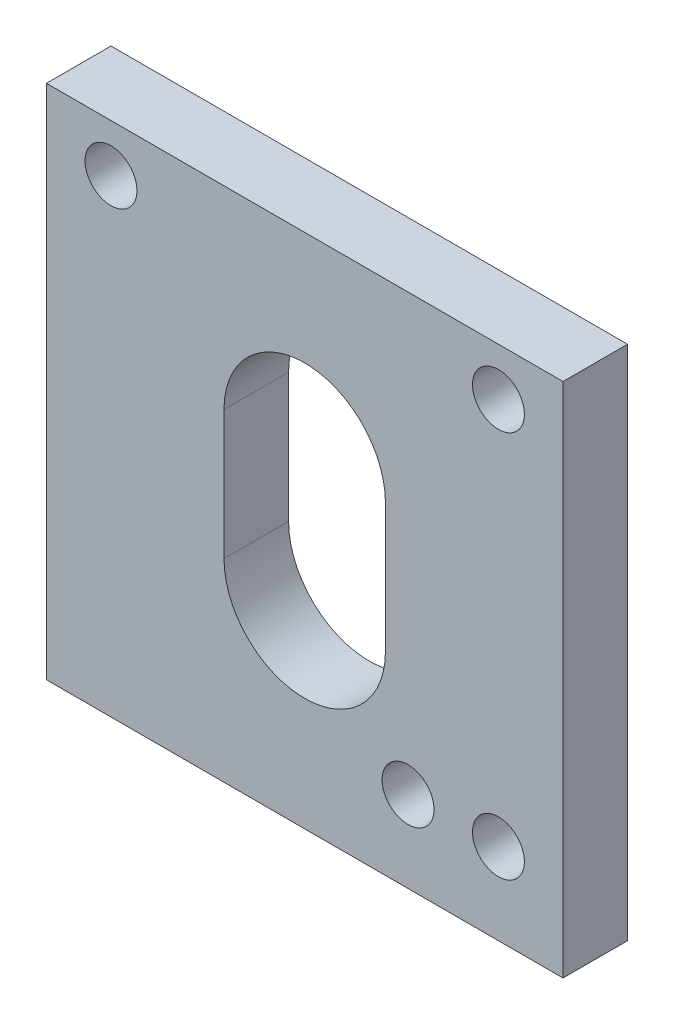
SolidWorks part; units mm, degrees
material "1060 Alloy"
ref_plane "Front Plane" through (0, 0, 0) normal (0, 0, 1) x (1, 0, 0)
ref_plane "Top Plane" through (0, 0, 0) normal (0, 1, 0) x (1, 0, 0)
ref_plane "Right Plane" through (0, 0, 0) normal (1, 0, 0) x (0, 0, -1)
sketch "Sketch1" plane through (0, 0, 0) normal (0, 0, 1) x (1, 0, 0)
  line L0 (0, 25.4) -> (0, -25.4) construction
  line L1 (-25.4, -25.4) -> (25.4, -25.4)
  line L2 (-25.4, -25.4) -> (-25.4, 25.4)
  line L3 (-25.4, 25.4) -> (25.4, 25.4)
  line L4 (25.4, -25.4) -> (25.4, 25.4)
  line L5 (-25.4, -25.4) -> (25.4, 25.4) construction
  line L6 (-25.4, 25.4) -> (25.4, -25.4) construction
  line L7 (25.4, 0) -> (-25.4, 0) construction
  line L8 (0, -6.35) -> (0, 6.35) construction
  line L9 (-7.9375, -6.35) -> (-7.9375, 6.35)
  line L10 (7.9375, -6.35) -> (7.9375, 6.35)
  circle A0 centre (-19.05, 20.701) radius 2.5527
  circle A1 centre (19.05, 20.701) radius 2.5527
  circle A2 centre (19.05, -17.399) radius 2.5527
  circle A3 centre (10.16, -17.399) radius 2.5527
  arc A4 (-7.9375, -6.35) -> (7.9375, -6.35) centre (0, -6.35) ccw
  arc A5 (7.9375, 6.35) -> (-7.9375, 6.35) centre (0, 6.35) ccw
  point P0 (0, 0)
  point P20 (0, 0)
  dimension "D3" = 5.1054
  dimension "D1" = 50.8
  dimension "D2" = 50.8
  dimension "D4" = 19.05
  dimension "D5" = 20.701
  dimension "D6" = 15.875
  dimension "D7" = 12.7
  dimension "D8" = 38.1
  dimension "D9" = 8.89
extrude "Boss-Extrude1" add sketch "Sketch1" along normal blind 6.35
